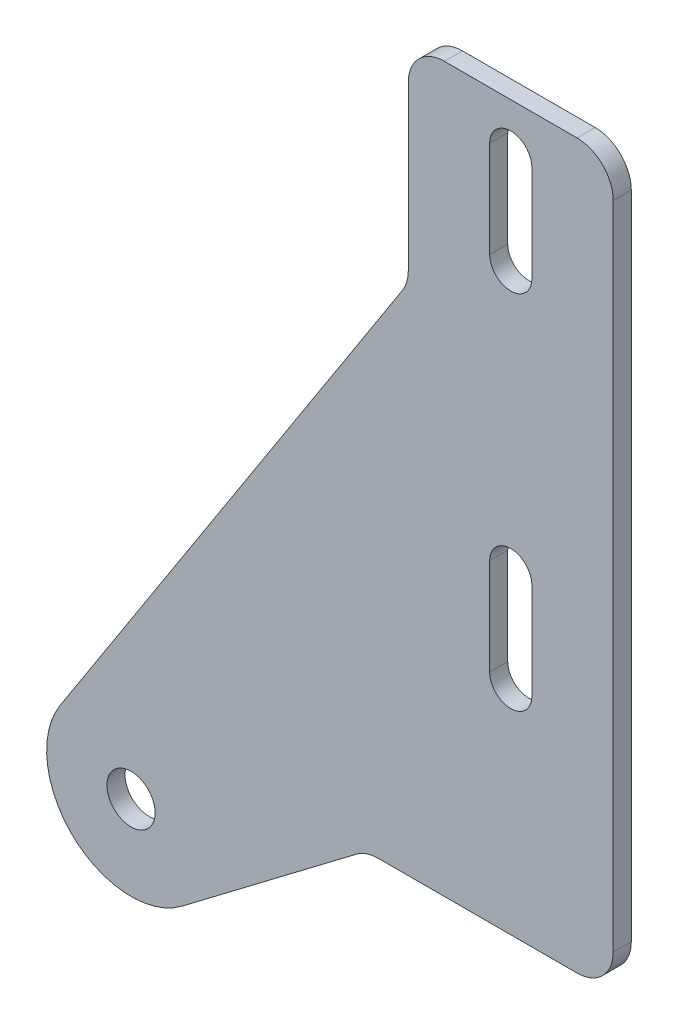
SolidWorks part; units mm, degrees
material "3.3535 (EN-AW 5754)"
ref_plane "Front" through (0, 0, 0) normal (0, 0, 1) x (1, 0, 0)
ref_plane "Top" through (0, 0, 0) normal (0, 1, 0) x (1, 0, 0)
ref_plane "Right" through (0, 0, 0) normal (1, 0, 0) x (0, 0, -1)
sketch "Esquisse1" plane through (0, 0, 0) normal (0, 0, 1) x (1, 0, 0)
  line L0 (0, 4) -> (0, -4) construction
  line L1 (1.75, 4) -> (1.75, -4)
  line L2 (-1.75, 4) -> (-1.75, -4)
  line L3 (0, 34) -> (0, 26) construction
  line L4 (1.75, 34) -> (1.75, 26)
  line L5 (-1.75, 34) -> (-1.75, 26)
  line L6 (-27.2709, -33.578) -> (-12, -22)
  line L7 (-8.5, 38) -> (8.5, 38)
  line L8 (-8.5, 38) -> (-8.5, 20.5572)
  line L9 (-12, -22) -> (8.5, -22)
  line L10 (8.5, 38) -> (8.5, -22)
  line L11 (-37.3819, -24.2048) -> (-8.5, 20.5572)
  arc A2 (1.75, 4) -> (-1.75, 4) centre (0, 4) ccw
  arc A3 (-1.75, -4) -> (1.75, -4) centre (0, -4) ccw
  arc A4 (1.75, 34) -> (-1.75, 34) centre (0, 34) ccw
  arc A5 (-1.75, 26) -> (1.75, 26) centre (0, 26) ccw
  circle A6 centre (-31.5, -28) radius 2
  arc A7 (-37.3819, -24.2048) -> (-27.2709, -33.578) centre (-31.5, -28) ccw
  point P3 (0, 0)
  point P8 (0, 30)
  point P24 (0, 38)
  dimension "D1" = 3.5
  dimension "D2" = 8
  dimension "D4" = 17
  dimension "D5" = 4
  dimension "D6" = 18
  dimension "D7" = 4
  dimension "D8" = 7
  dimension "D9" = 31.5
  dimension "D10" = 6
  dimension "D3" = 30
  dimension "D11" = 20
  dimension "D12" = 12
base flange "Tôle de base pliée1" sketch "Esquisse1" thickness 1.5 reverse thickness direction no parameters "D1"=5
fillet "Congé1" radius 3 5 edges at (-8.5, 20.5572, -0.75) (-12, -22, -0.75) (8.5, -22, -0.75) (-8.5, 38, -0.75) (8.5, 38, -0.75)
sketch "Lignes de pliage1" [suppressed] plane through (0, 0, 0) normal (0, 1, 0) x (1, 0, 0)
sketch "Cube de visualisation1" [suppressed] plane through (0, 0, 0) normal (0, 1, 0) x (1, 0, 0)
sheet metal parameters "Tôlerie1" thickness 1.5 parameters "D1"=5
flat pattern "Etat déplié1" [suppressed]
sketch "Lignes de pliage2" plane through (0, 0, 0) normal (0, 1, 0) x (1, 0, 0)
sketch3d "Cube de visualisation2" [suppressed]
  line L0 (26.1257, -20.3986, 0) -> (62.1603, 54.1737, 0) construction
  line L1 (-9.3482, -3.2571, 0) -> (26.6865, 71.3153, 0) construction
  line L2 (26.1257, -20.3986, 0) -> (-9.3482, -3.2571, 0) construction
  line L3 (62.1603, 54.1737, 0) -> (26.6865, 71.3153, 0) construction
